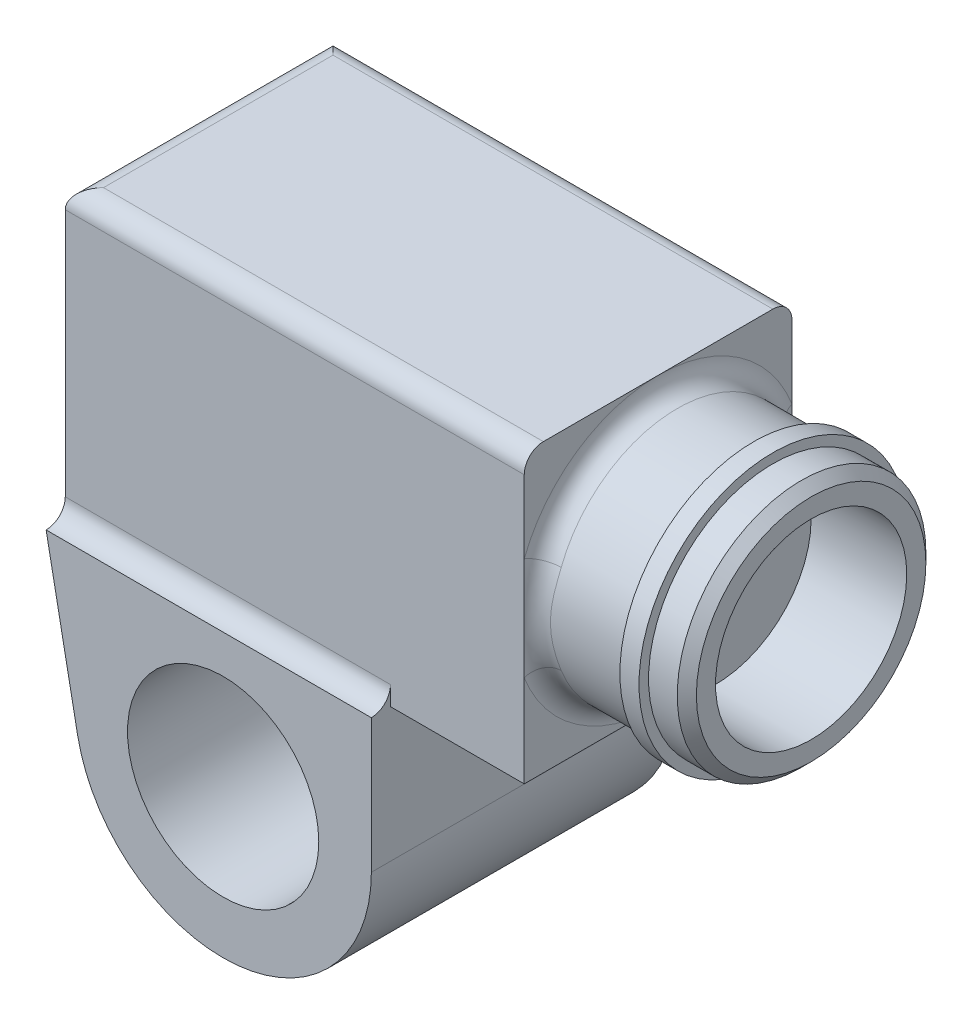
SolidWorks part; units mm, degrees
material "1060 Alloy"
ref_plane "Front" through (0, 0, 0) normal (0, 0, 1) x (1, 0, 0)
ref_plane "Top" through (0, 0, 0) normal (0, 1, 0) x (1, 0, 0)
ref_plane "Right" through (0, 0, 0) normal (1, 0, 0) x (0, 0, -1)
sketch "Sketch1" plane through (0, 0, 0) normal (1, 0, 0) x (0, 0, -1)
  line L1 (-70, 75) -> (70, 75)
  line L2 (-70, 75) -> (-70, -75)
  line L3 (-70, -75) -> (70, -75)
  line L4 (70, 75) -> (70, -75)
  line L5 (-70, 75) -> (70, -75) construction
  line L6 (-70, -75) -> (70, 75) construction
  point P0 (0, 0)
  dimension "D1" = 140
  dimension "D2" = 150
extrude "Boss-Extrude1" add sketch "Sketch1" along normal blind 240
sketch "Sketch2" plane through (240, 0, 0) normal (1, 0, 0) x (0, 0, -1)
  circle A0 centre (0, 0) radius 65
  dimension "D1" = 130
extrude "Boss-Extrude2" add sketch "Sketch2" along normal blind 50
sketch "Sketch3" plane through (290, 0, 0) normal (1, 0, 0) x (0, 0, -1)
  circle A0 centre (0, 0) radius 70
  dimension "D1" = 140
extrude "Boss-Extrude3" add sketch "Sketch3" along normal blind 10
sketch "Sketch4" plane through (0, 0, 0) normal (0, 0, 1) x (1, 0, 0)
  line L0 (170.0572, -145) -> (170.0572, -75)
  line L1 (240, -75) -> (0, -75) construction
  line L2 (16.4811, -159.7877) -> (0, -75)
  line L3 (0, 75) -> (0, -75) construction
  line L4 (0, -75) -> (170.0572, -75)
  arc A0 (16.4811, -159.7877) -> (170.0572, -145) centre (92.5572, -145) ccw
  circle A1 centre (92.5572, -145) radius 50
  dimension "D1" = 155
  dimension "D4" = 100
  dimension "D2" = 70
  dimension "D3" = 191
extrude "Boss-Extrude4" add sketch "Sketch4" along normal mid plane 160
fillet "Fillet1" radius 10 3 edges at (85.0286, -75, -70) (240, 0, -65) (85.0286, -75, 70)
sketch "Sketch5" plane through (300, 0, 0) normal (1, 0, 0) x (0, 0, -1)
  circle A0 centre (0, 0) radius 65
  dimension "D1" = 130
extrude "Boss-Extrude5" add sketch "Sketch5" along normal blind 20
fillet "Fillet4" radius 10 3 edges at (0, 75, 0) (120, 75, -70) (120, 75, 70)
sketch "Sketch6" plane through (320, 0, 0) normal (1, 0, 0) x (0, 0, -1)
  circle A0 centre (0, 0) radius 50
  dimension "D1" = 100
extrude "Cut-Extrude1" cut sketch "Sketch6" against normal blind 50
chamfer "Chamfer1" distance 5 angle 45 1 edges at (320, 0, -65)
